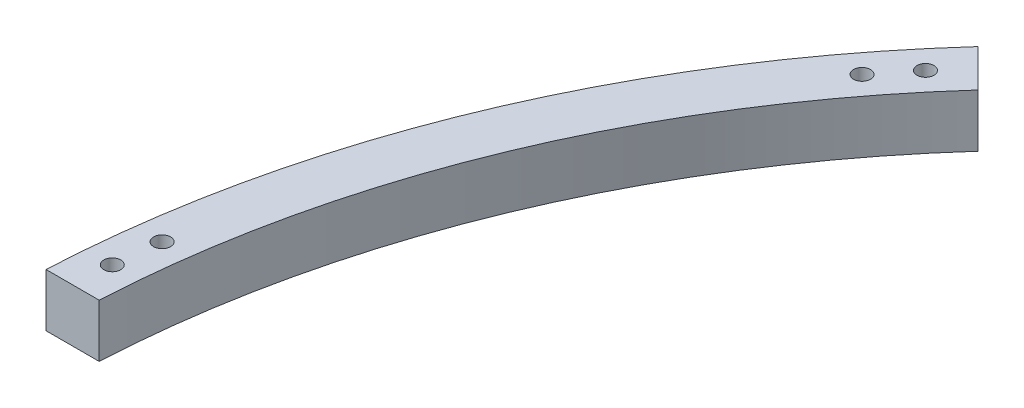
SolidWorks part; units mm, degrees
ref_plane "Front Plane" through (0, 0, 0) normal (0, 0, 1) x (1, 0, 0)
ref_plane "Top Plane" through (0, 0, 0) normal (0, 1, 0) x (1, 0, 0)
ref_plane "Right Plane" through (0, 0, 0) normal (1, 0, 0) x (0, 0, -1)
sketch "Sketch1" plane through (0, 0, 0) normal (0, 1, 0) x (1, 0, 0)
  line L1 (0, 200) -> (0, -200) construction
  line L6 (-200, 0) -> (200, 0) construction
  line L7 (-10, 199.7498) -> (-10, -199.7498) construction
  line L12 (-10, 199.7498) -> (-10, 189.7367)
  line L13 (-199.7498, 10) -> (199.7498, 10) construction
  line L14 (-199.7498, 10) -> (-189.7367, 10)
  line L15 (-141.4214, 141.4214) -> (141.4214, -141.4214) construction
  line L16 (-148.3155, 134.1734) -> (134.1734, -148.3155)
  arc A3 (-10, 199.7498) -> (-199.7498, 10) centre (0, 0) ccw
  arc A4 (-10, 189.7367) -> (-189.7367, 10) centre (0, 0) ccw
  arc A5 (-190, 0) -> (-189.7367, 10) centre (0, 0) ccw construction
  arc A6 (-200, 0) -> (-199.7498, 10) centre (0, 0) ccw construction
  circle A7 centre (0, 0) radius 195 construction
  dimension "D1" = 190
  dimension "D2" = 200
  dimension "D4" = 10
  dimension "D5" = 5
  dimension "D3" = 10
  dimension "D6" = 10
sketch "Sketch14" [suppressed] plane through (0, 0, 0) normal (0, 1, 0) x (1, 0, 0)
  line L0 (-200, 10) -> (200, 10) construction
  line L1 (-10, 200) -> (-10, -200) construction
  line L2 (-200, 10) -> (-189.7367, 10)
  line L3 (-10, 200) -> (-10, 189.7367)
  circle A0 centre (0, 0) radius 200 construction
  circle A1 centre (0, 0) radius 190 construction
  arc A2 (-10, 199.7498) -> (-199.7498, 10) centre (0, 0) ccw
  arc A3 (-10, 189.7367) -> (-189.7367, 10) centre (0, 0) ccw
sketch "roll" plane through (0, 0, 0) normal (0, 1, 0) x (1, 0, 0)
  line L0 (0, -195) -> (0, 195) construction
  dimension "D1" = 390
ref_axis "Axis1" through (0, -148.0362, 0) along (0, 1, 0)
extrude "base" add sketch "Sketch1" along normal mid plane 10 contours A4 L15 A3 L14 region at (-176.7216, 0, -73.2005)
sketch "Sketch25" plane through (0, 5, 0) normal (0, 1, 0) x (1, 0, 0)
  line L0 (-200, 0) -> (200, 0) construction
  line L1 (0, 200) -> (0, -200) construction
  line L2 (-200, 0) -> (200, 0)
  line L3 (0, 200) -> (0, -200)
  line L4 (0, 0) -> (-194.258, 16.9954) construction
  line L5 (0, 0) -> (-193.3317, 25.4526) construction
  line L6 (-141.4214, 141.4214) -> (141.4214, -141.4214) construction
  line L7 (-141.4214, 141.4214) -> (141.4214, -141.4214)
  line L8 (0, 0) -> (-149.3787, 125.3436) construction
  line L9 (0, 0) -> (-154.7039, 118.7085) construction
  circle A0 centre (0, 0) radius 195 construction
  circle A1 centre (0, 0) radius 195 construction
  dimension "D1" = 5
  dimension "D2" = 7.5
  dimension "D3" = 5
  dimension "D4" = 7.5
ref_plane "Plane1" through (0, 0, 0) normal (0.7071, 0, -0.7071) x (0.7071, 0, 0.7071)
hole_wizard "Ø3.2 (3.2) Diameter Hole1" positions "Sketch28" profile "Sketch29" hole size "Ø3.2" standard "ISO" end condition through all
sketch "Sketch28" plane through (0, 5, 0) normal (0, 1, 0) x (1, 0, 0)
  point P0 (-194.258, 16.9954)
  point P3 (-149.3787, 125.3436)
  point P6 (-154.7039, 118.7085)
  point P9 (-193.3317, 25.4526)
sketch "Sketch29" plane through (-194.258, 5, -16.9954) normal (1, 0, 0) x (0, 0, 1)
  line L0 (0, 0) -> (0, 10)
  line L1 (0, 10) -> (1.6, 10)
  line L2 (1.6, 10) -> (1.6, 0)
  line L5 (1.6, 0) -> (0, 0)
  line L11 (0, -6.35) -> (0, 107.95) construction
  dimension "Thru Hole Dia." = 3.2
  dimension "Thru Hole Depth" = 10
